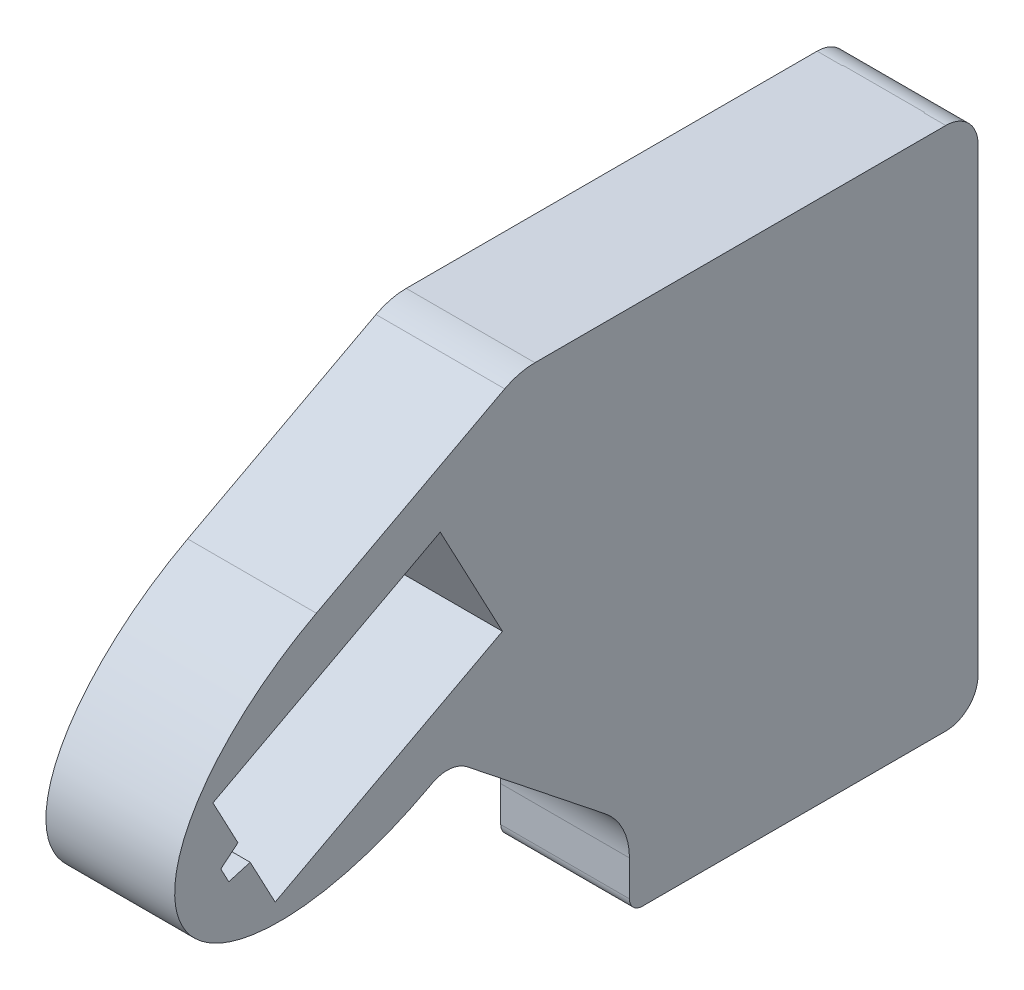
SolidWorks part; units mm, degrees
ref_plane "前视基准面" through (0, 0, 0) normal (0, 0, 1) x (1, 0, 0)
ref_plane "上视基准面" through (0, 0, 0) normal (0, 1, 0) x (1, 0, 0)
ref_plane "右视基准面" through (0, 0, 0) normal (1, 0, 0) x (0, 0, -1)
sketch "草图1" plane through (0, 0, 0) normal (1, 0, 0) x (0, 0, -1)
  line L0 (-6.1151, -25.0862) -> (-2.2324, -32.3885)
  line L1 (-2.2324, -32.3885) -> (-4.8912, -34.5997)
  line L2 (-4.8912, -34.5997) -> (-3.6466, -36.9404)
  line L3 (34.0384, -15.4017) -> (29.2028, -6.3074)
  line L4 (-0.3267, -35.9727) -> (-3.6466, -36.9404)
  line L5 (-0.3267, -35.9727) -> (3.556, -43.275)
  line L6 (34.0384, -15.4017) -> (38.8739, -24.4961)
  line L8 (29.2028, -6.3074) -> (-6.1151, -25.0862)
  line L9 (38.8739, -24.4961) -> (3.556, -43.275)
  line L10 (58.6056, -64.8541) -> (58.6056, -70.3639)
  line L11 (9.9591, -7.6007) -> (39.2215, 7.9584)
  line L12 (29.2028, -6.3074) -> (38.8739, -24.4961)
  line L14 (29.2028, -6.3074) -> (-6.1151, -25.0862)
  line L16 (27.1417, -39.9166) -> (27.9382, -39.4931)
  line L17 (60.6056, -72.3639) -> (107.764, -72.3639)
  line L18 (112.764, -67.3639) -> (112.764, 4.1289)
  line L19 (107.764, 9.1289) -> (43.9163, 9.1289)
  line L21 (54.8274, -57.0253) -> (33.3964, -39.9935)
  circle A11 centre (39.9175, -17.9386) radius 1.8
  circle A12 centre (35.2228, -9.1091) radius 1.8
  circle A13 centre (-1.9215, -40.1848) radius 1.8
  circle A14 centre (-6.6163, -31.3553) radius 1.8
  arc A15 (54.8274, -57.0253) -> (58.6056, -64.8541) centre (48.6056, -64.8541) cw
  arc A16 (39.2215, 7.9584) -> (43.9163, 9.1289) centre (43.9163, -0.8711) cw
  arc A17 (107.764, -72.3639) -> (112.764, -67.3639) centre (107.764, -67.3639) ccw
  arc A18 (112.764, 4.1289) -> (107.764, 9.1289) centre (107.764, 4.1289) ccw
  arc A19 (33.3964, -39.9935) -> (27.9382, -39.4931) centre (30.2855, -43.9079) ccw
  arc A20 (58.6056, -70.3639) -> (60.6056, -72.3639) centre (60.6056, -70.3639) ccw
  ellipse E0 centre (18.5504, -23.7586) end of major axis (-10.8294, -39.3802) minor radius 18.3 (9.9591, -7.6007) -> (27.1417, -39.9166) ccw
  point P3 (34.0384, -15.4017)
  point P10 (6.3614, -10.4197)
  point P54 (-4.2689, -35.7701)
  dimension "D1" = 10
  dimension "D2" = 5
  dimension "D3" = 5
  dimension "D4" = 2
extrude "凸台-拉伸1" add sketch "草图1" along normal blind 20 contours L18 A18 L19 A16 L11 E0 L16 A19 L21 A15 L10 A20 L17 A17
extrude "切除-拉伸2" cut sketch "草图1<11>" along normal blind 20 contours L9 L5 L4 L2 L1 L0 L14 L12
sketch "草图1<11>" plane through (0, 0, 0) normal (1, 0, 0) x (0, 0, -1) same geometry as "草图1"
extrude "切除-拉伸3" cut sketch "草图1<12>" along normal blind 11 contours A11 | A14 | A13 | A12 region at (0, -17.9386, -39.9175)
sketch "草图1<12>" plane through (0, 0, 0) normal (1, 0, 0) x (0, 0, -1) same geometry as "草图1"
sketch "草图3" plane through (0, 0, 0) normal (0, 1, 0) x (1, 0, 0)
  line L0 (0, 112.764) -> (20, 112.764)
  line L3 (0, 112.764) -> (-10.0484, 112.764)
  line L9 (10, 112.764) -> (-10.0484, 112.764)
  line L10 (30, 97.764) -> (30, 97.4499)
  line L11 (30, 97.764) -> (30, 97.4499)
  line L14 (10, 81.164) -> (10, 74.364)
  circle A12 centre (10, 102.764) radius 1.6
  circle A13 centre (10, 92.764) radius 1.6
  circle A14 centre (10, 82.764) radius 1.6
  circle A15 centre (10, 72.764) radius 1.6
  circle A16 centre (10, 64.764) radius 1.6
  point P1 (0, 0)
  dimension "D1" = 10
  dimension "D5" = 10
  dimension "D6" = 10
  dimension "D2" = 10
  dimension "D7" = 8
extrude "切除-拉伸5" cut sketch "草图3" against normal through all both and the other way through all contours A12 | A13 | A14 | A15 | A16
sketch "草图5" plane through (0, 0, 0) normal (0, 1, 0) x (1, 0, 0)
  line L0 (3.9558, 107.8663) -> (16.6135, 107.8663)
  line L1 (16.6135, 107.8663) -> (16.6135, 61.2825)
  line L2 (16.6135, 61.2825) -> (3.9558, 61.2825)
  line L3 (3.9558, 61.2825) -> (3.9558, 107.8663)
extrude "凸台-拉伸5" add sketch "草图5" along normal through all contours L3 L0 L1 L2
